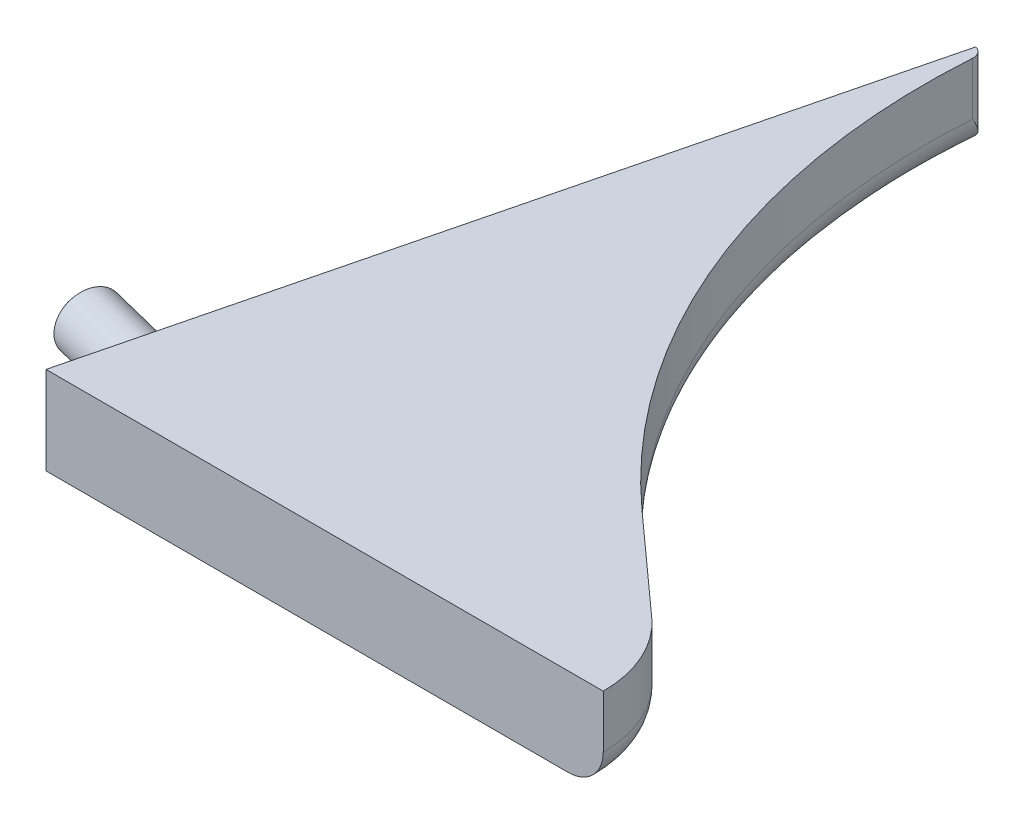
SolidWorks part; units mm, degrees
material "ABS"
ref_plane "Front Plane" through (0, 0, 0) normal (0, 0, 1) x (1, 0, 0)
ref_plane "Top Plane" through (0, 0, 0) normal (0, 1, 0) x (1, 0, 0)
ref_plane "Right Plane" through (0, 0, 0) normal (1, 0, 0) x (0, 0, -1)
sketch "Sketch1" plane through (0, 0, 0) normal (0, 1, 0) x (1, 0, 0)
  line L0 (0, 0) -> (12.0961, 48.5148) construction
  line L1 (0, 0) -> (31.6928, 0)
  line L2 (23.8549, 10.0393) -> (35, 0) construction
  line L3 (23.8549, 10.0393) -> (29.4794, 4.9728)
  line L4 (0, 0) -> (10.5532, 42.3264)
  arc A0 (11.0235, 41.681) -> (23.8549, 10.0393) centre (50, 39.0643) ccw
  arc A1 (31.6928, 0) -> (29.4794, 4.9728) centre (25, 0) ccw
  arc A2 (11.0235, 41.681) -> (10.5532, 42.3264) centre (10.4026, 41.7227) ccw
  dimension "D1" = 76
  dimension "D2" = 50
  dimension "D3" = 35
  dimension "D4" = 10
  dimension "D5" = 7
extrude "Boss-Extrude1" add sketch "Sketch1" along normal mid plane 5
sketch "Sketch2" plane through (0, 0, 0) normal (-0.9703, 0, -0.2419) x (-0.2419, 0, 0.9703)
  circle A0 centre (-5, 0) radius 1.625
  dimension "D1" = 3.25
  dimension "D2" = 5
extrude "Boss-Extrude2" add sketch "Sketch2" along normal blind 5.5
chamfer "Chamfer1" distance 0.5 angle 45 1 edges at (-4.5201, 0, -4.6053)
sketch "Sketch3" plane through (0, 0, 0) normal (0, 1, 0) x (1, 0, 0)
  line L0 (0.8165, 3.2747) -> (0.7076, 2.8381)
  line L1 (-4.035, 4.4844) -> (0.8165, 3.2747) construction
  line L2 (10.5532, 42.3264) -> (0, 0) construction
  line L3 (-4.035, 4.4844) -> (0.8165, 3.2747) construction
  line L8 (0.791, 2.9563) -> (0.8632, 3.0042)
  line L9 (10.5532, 42.3264) -> (0, 0) construction
  line L10 (0.7076, 2.8381) -> (0.9017, 2.7897) construction
  arc A0 (0.8165, 3.2747) -> (0.8632, 3.0042) centre (0.7802, 3.1292) cw
  arc A1 (0.7076, 2.8381) -> (0.791, 2.9563) centre (0.9017, 2.7897) cw
  dimension "D3" = 0.15
  dimension "D1" = 0.2
  dimension "D2" = 0.45
ref_axis "Axis1" through (-4.3821, 0, -6.2456) along (0.9703, 0, 0.2419)
revolve "Cut-Revolve4" cut sketch "Sketch3" angle 360 about axis through (-4.3821, 0, -6.2456) along (0.9703, 0, 0.2419)
fillet "Fillet2" radius 2 3 edges at (31.1145, -2.5, -2.7216) (26.6672, -2.5, -7.506) (13.7991, -2.5, -24.384)
